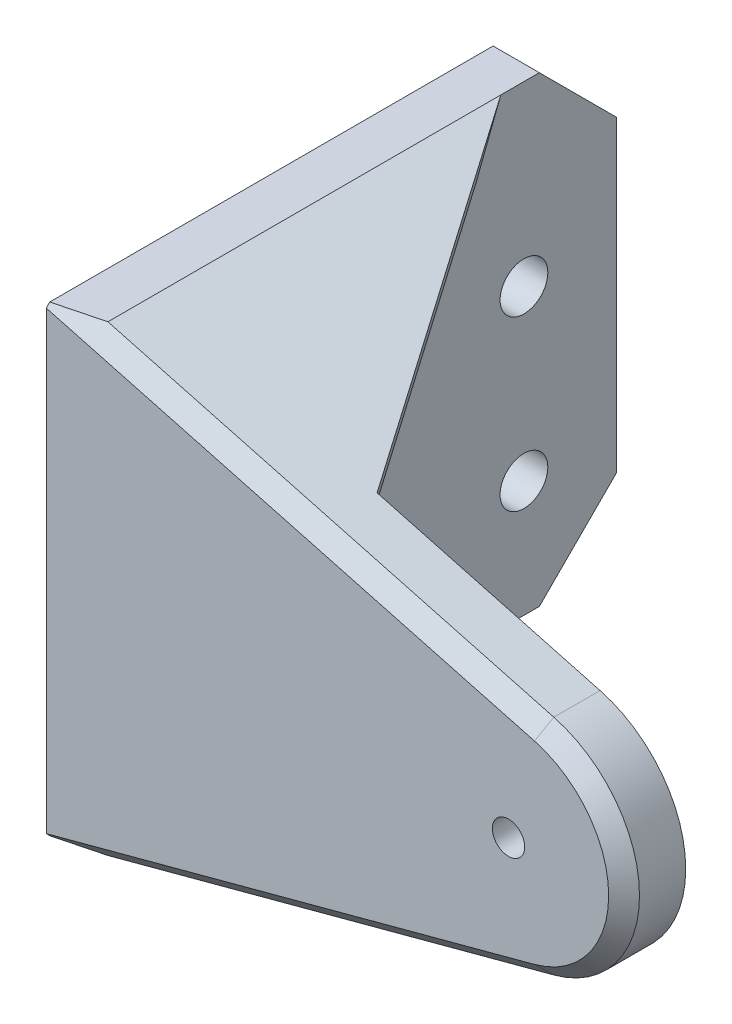
SolidWorks part; units mm, degrees
ref_plane "Front Plane" through (0, 0, 0) normal (0, 0, 1) x (1, 0, 0)
ref_plane "Top Plane" through (0, 0, 0) normal (0, 1, 0) x (1, 0, 0)
ref_plane "Right Plane" through (0, 0, 0) normal (1, 0, 0) x (0, 0, -1)
sketch "Sketch1" plane through (0, 0, 0) normal (0, 0, 1) x (1, 0, 0)
  line L0 (-24.444, 5.5562) -> (-24.444, -9.4438)
  line L1 (5.556, 5.5562) -> (-24.444, 5.5562) construction
  line L2 (-24.444, 5.5562) -> (-24.444, 20.5562)
  line L3 (-24.444, -9.4438) -> (-21.444, -9.4438)
  line L4 (-21.444, -9.4438) -> (7.4973, -1.6881)
  line L5 (-24.444, 20.5562) -> (-21.444, 20.5562)
  line L6 (-21.444, 20.5562) -> (7.4973, 12.8006)
  circle A1 centre (5.556, 5.5562) radius 1.984
  circle A2 centre (5.556, 5.5562) radius 7.5
  dimension "D1" = 15
  dimension "D2" = 30
  dimension "D3" = 15
  dimension "D4" = 15
  dimension "D5" = 3
  dimension "D6" = 3
extrude "Boss-Extrude1" add sketch "Sketch1" along normal blind 4 contours A2 L1 L0 L3 L4 | L1 A2 L6 L5 L2 | A1 A2 | A1 region at (-13.0294, -0.9504, 0) region at (-13.0294, 12.0629, 0) region at (5.556, 7.4841, 0) region at (1.1195, 11.3382, 0)
extrude "Cut-Extrude1" cut sketch "Sketch1<3>" along normal blind 1 contours A1
sketch "Sketch1<3>" plane through (0, 0, 0) normal (0, 0, 1) x (1, 0, 0) same geometry as "Sketch1"
sketch "Sketch2" plane through (0, 0, 4) normal (0, 0, 1) x (1, 0, 0)
  circle A0 centre (5.556, 5.5562) radius 1.984 construction
  circle A1 centre (5.556, 5.5562) radius 1.984
  circle A2 centre (5.556, 5.5562) radius 1.05
  dimension "D1" = 2.1
extrude "Cut-Extrude2" cut sketch "Sketch2" against normal up to next contours A2 region at (5.556, 5.5562, 4)
sketch "Sketch3" plane through (0, 0, 0) normal (0, 0, -1) x (-1, 0, 0)
  line L0 (21.444, 20.5562) -> (21.444, -9.4438)
  line L1 (21.444, -9.4438) -> (24.444, -9.4438)
  line L2 (24.444, -9.4438) -> (24.444, 20.5562)
  line L3 (24.444, 20.5562) -> (21.444, 20.5562)
extrude "Boss-Extrude2" add sketch "Sketch3" along normal blind 30
sketch "Sketch4" plane through (3.7028, 13.8175, 0) normal (0.2588, 0.9659, 0) x (0.9659, -0.2588, 0)
  line L0 (-26.034, 22.5) -> (-11.0528, 0)
  line L1 (-26.034, 0) -> (3.9284, 0) construction
  line L3 (-26.034, 15) -> (-26.034, 30) construction
  line L4 (-26.034, 30) -> (-26.034, 0) construction
  line L5 (-11.0528, 0) -> (-11.0528, -0.5)
  line L6 (-11.0528, -0.5) -> (-26.034, -0.5)
  line L7 (-26.034, -4) -> (-26.034, 0) construction
  line L8 (-26.034, -0.5) -> (-26.034, 22.5)
  dimension "D1" = 0.5
extrude "Boss-Extrude3" add sketch "Sketch4" against normal blind 4
ref_axis "Axis1" through (5.556, 5.5562, 0) along (-1, 0, 0)
ref_plane "Plane1" through (0, 5.5562, 0) normal (0, 1, 0) x (-1, 0, 0)
chamfer "Chamfer1" distance 5 angle 45 1 edges at (-21.444, 3.4857, 0)
chamfer "Chamfer2" distance 5 angle 45 2 edges at (-22.944, -9.4438, -30) (-22.944, 20.5562, -30)
chamfer "Chamfer3" distance 1 angle 45 3 edges at (-6.9733, -5.5659, 4) (13.056, 5.5562, 4) (-6.9733, 16.6784, 4)
sketch "Sketch6" plane through (-21.444, 0, 0) normal (1, 0, 0) x (0, 0, -1)
  line L0 (30, 9.0472) -> (9.61, 9.0472) construction
  line L1 (30, 15.5562) -> (30, -4.4438) construction
  line L2 (30, -1.8898) -> (9.5502, -1.8898) construction
  line L3 (24, 9.0472) -> (24, -1.8898) construction
  line L4 (11, 9.0472) -> (11, -1.8898) construction
  circle A0 centre (11, 9.0472) radius 1.55
  circle A1 centre (24, 9.0472) radius 1.55
  circle A2 centre (11, -1.8898) radius 1.55
  circle A3 centre (24, -1.8898) radius 1.55
  dimension "D1" = 3.1
  dimension "D2" = 3.1
  dimension "D3" = 3.1
  dimension "D4" = 3.1
  dimension "D5" = 6
  dimension "D6" = 13
extrude "Cut-Extrude3" cut sketch "Sketch6" against normal up to next
